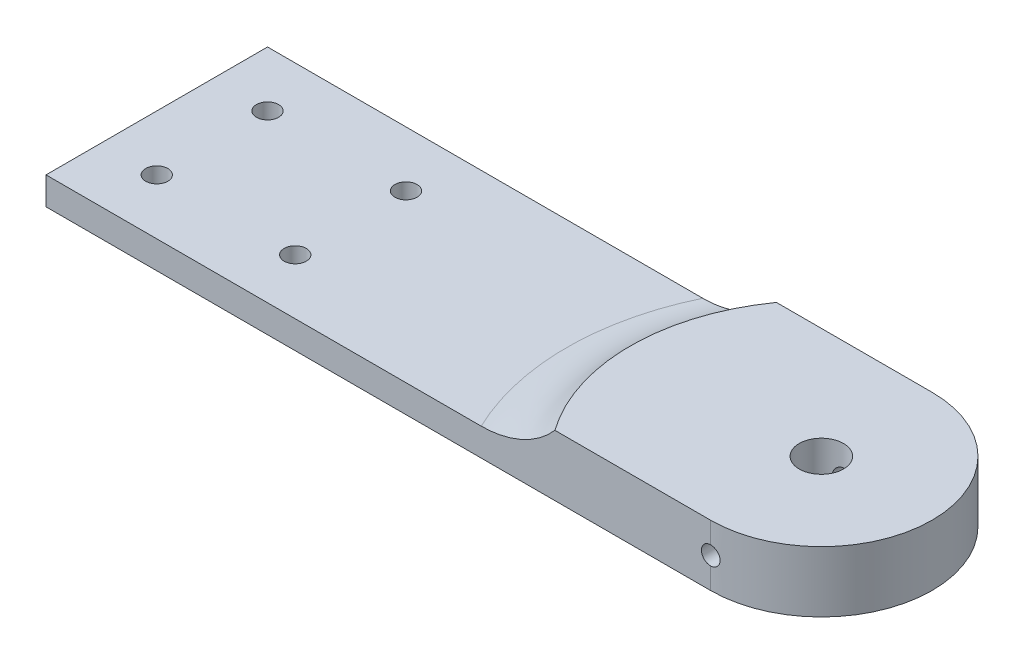
SolidWorks part; units mm, degrees
material "1060 Alloy"
ref_plane "Front Plane" through (0, 0, 0) normal (0, 0, 1) x (1, 0, 0)
ref_plane "Top Plane" through (0, 0, 0) normal (0, 1, 0) x (1, 0, 0)
ref_plane "Right Plane" through (0, 0, 0) normal (1, 0, 0) x (0, 0, -1)
sketch "Sketch1" plane through (0, 0, 0) normal (0, 1, 0) x (1, 0, 0)
  line L0 (-120, 20) -> (20, 20)
  line L1 (20, 20) -> (20, -5)
  line L2 (20, -5) -> (-120, -5) construction
  line L3 (-120, -5) -> (-120, 20)
  line L4 (20, -5) -> (20, -20)
  line L5 (20, -20) -> (-120, -20)
  line L6 (-120, -20) -> (-120, -5)
  line L7 (20, -10) -> (-110, -10) construction
  line L8 (-110, -10) -> (-110, -5) construction
  line L9 (-110, -5) -> (-110, 10) construction
  line L10 (-110, 10) -> (20, 10) construction
  circle A0 centre (0, 0) radius 4
  circle A1 centre (-110, 10) radius 2
  circle A2 centre (-85, 10) radius 2
  circle A3 centre (-85, -10) radius 2
  circle A4 centre (-110, -10) radius 2
  arc A5 (0, -20) -> (0, 20) centre (0, 0) ccw
  dimension "D1" = 8
  dimension "D7" = 4
  dimension "D2" = 20
  dimension "D3" = 25
  dimension "D4" = 20
  dimension "D5" = 15
  dimension "D6" = 140
  dimension "D9" = 25
  dimension "D8" = 10
extrude "Boss-Extrude1" add sketch "Sketch1" along normal blind 11 contours L5 A5 L0 L3 L6 A4 A3 A2 A1 A0 region at (-52.1353, 0, 0)
sketch "Sketch4" plane through (0, 11, 0) normal (0, 1, 0) x (1, 0, 0)
  line L0 (-28.1114, 20) -> (-120, 20)
  line L1 (-120, 20) -> (-120, -20)
  line L2 (-120, -20) -> (-28.1114, -20)
  arc A1 (-28.1114, 20) -> (-28.1114, -20) centre (0, 0) ccw
  dimension "D1" = 69
extrude "Cut-Extrude1" cut sketch "Sketch4" against normal offset from surface (6 mm away) 5 up to face at (-110, 0, 12)
fillet "Fillet2" radius 14 1 edges at (-34.5, 5, 0)
hole_wizard "M4 Tapped Hole1" positions "Sketch2" profile "Sketch3" tap size "M4" standard "ISO" end condition through all
sketch "Sketch2" plane through (0, 0, -20) normal (0, 0, -1) x (-1, 0, 0)
  line L0 (0, 55) -> (0, -55) construction
  line L1 (0, 11) -> (0, 0) construction
  point P0 (0, 5.5)
  point P11 (0, 5.5)
cosmetic thread "Hole Thread1" parameters "D2"=4
sketch "Sketch3" plane through (0, 5.5, -20) normal (1, 0, 0) x (0, 1, 0)
  line L0 (0, 0) -> (0, 40)
  line L1 (0, 40) -> (1.65, 40)
  line L2 (1.65, 40) -> (1.65, 0)
  line L5 (1.65, 0) -> (0, 0)
  line L11 (0, -6.35) -> (0, 107.95) construction
  dimension "Thru Tap Drill Dia." = 3.3
  dimension "Thru Tap Drill Depth" = 40
